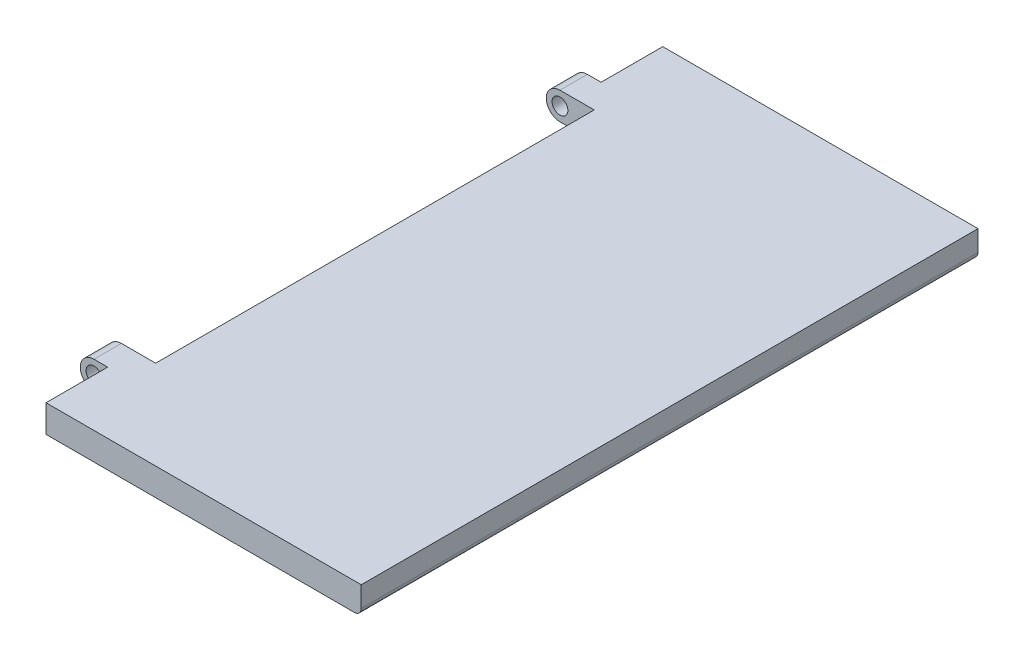
SolidWorks part; units mm, degrees
ref_plane "前视基准面" through (0, 0, 0) normal (0, 0, 1) x (1, 0, 0)
ref_plane "上视基准面" through (0, 0, 0) normal (0, 1, 0) x (1, 0, 0)
ref_plane "右视基准面" through (0, 0, 0) normal (1, 0, 0) x (0, 0, -1)
other "Configuration Table"
sketch "草图2" plane through (0, 0, 0) normal (0, 0, 1) x (1, 0, 0)
  line L1 (0, 0) -> (46, 0)
  line L2 (0, 0) -> (0, 4)
  line L3 (0, 4) -> (46, 4)
  line L4 (46, 0) -> (46, 4)
  dimension "D1" = 4
  dimension "D2" = 46
extrude "凸台-拉伸1" add sketch "草图2" along normal blind 90 contours L2 L1 L4 L3
sketch "草图3" plane through (0, 0, 0) normal (-1, 0, 0) x (0, 0, 1)
  line L0 (90, 0) -> (0, 0) construction
  line L1 (14, 0) -> (21, 0) construction
  line L2 (14, 0) -> (14, 4) construction
  line L3 (14, 4) -> (21, 4) construction
  line L4 (21, 0) -> (21, 4) construction
  line L5 (90, 4) -> (0, 4) construction
  line L6 (0, 0) -> (0, 4) construction
  line L8 (9, 4) -> (13, 4)
  line L9 (9, 4) -> (9, 0)
  line L10 (9, 0) -> (13, 0)
  line L11 (13, 4) -> (13, 0)
  dimension "D1" = 7
  dimension "D2" = 14
  dimension "D3" = 4
  dimension "D4" = 1
extrude "凸台-拉伸2" add sketch "草图3" along normal blind 4 contours L9 L8 L11 L10
fillet "圆角1" radius 2 2 edges at (-4, 4, 11) (-4, 0, 11)
sketch "草图4" plane through (0, 0, 13) normal (0, 0, 1) x (1, 0, 0)
  line L0 (-2, 4) -> (-2, 0) construction
  circle A0 centre (-2, 2) radius 1.15
  dimension "D1" = 2.3
extrude "切除-拉伸1" cut sketch "草图4" against normal up to next
ref_plane "基准面1" through (0, 0, 45) normal (0, 0, -1) x (-1, 0, 0)
mirror "镜向3" about plane through (0, 0, 45) normal (0, 0, -1) of "圆角1", "凸台-拉伸2", "切除-拉伸1"
fillet "圆角2" radius 1 1 edges at (46, 0, 45)
chamfer "倒角1" distance 3 angle 45 1 edges at (0, 4, 45)
